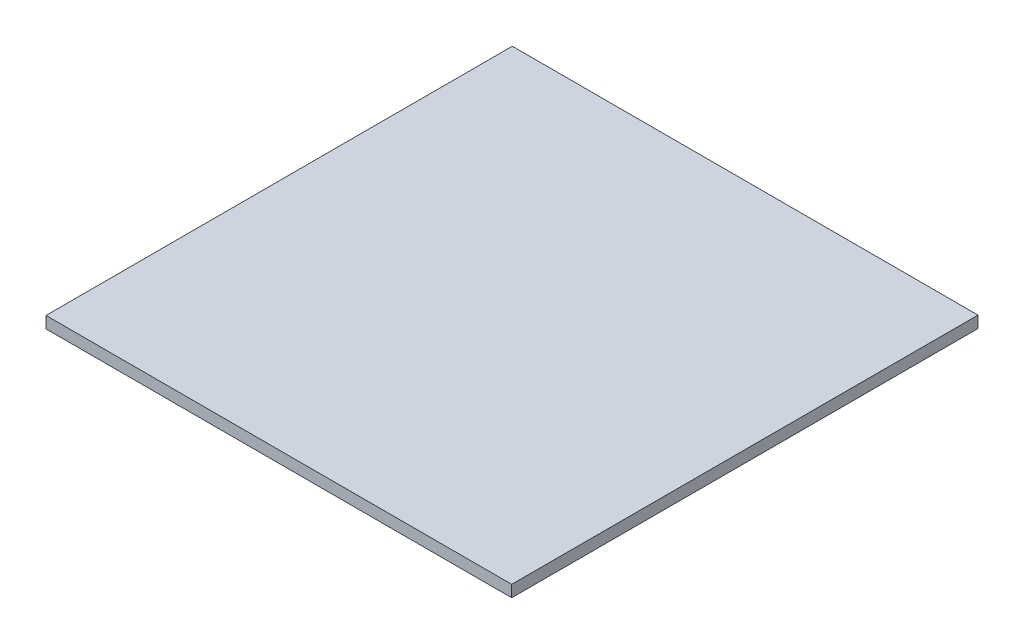
SolidWorks part; units mm, degrees
ref_plane "Спереди" through (0, 0, 0) normal (0, 0, 1) x (1, 0, 0)
ref_plane "Сверху" through (0, 0, 0) normal (0, 1, 0) x (1, 0, 0)
ref_plane "Справа" through (0, 0, 0) normal (1, 0, 0) x (0, 0, -1)
sketch "Эскиз1" plane through (0, 0, 0) normal (0, 1, 0) x (1, 0, 0)
  line L1 (0, 0) -> (199.7407, 0)
  line L2 (0, 0) -> (0, 200)
  line L3 (0, 200) -> (199.7407, 200)
  line L4 (199.7407, 0) -> (199.7407, 200)
extrude "Бобышка-Вытянуть1" add sketch "Эскиз1" along normal blind 5
